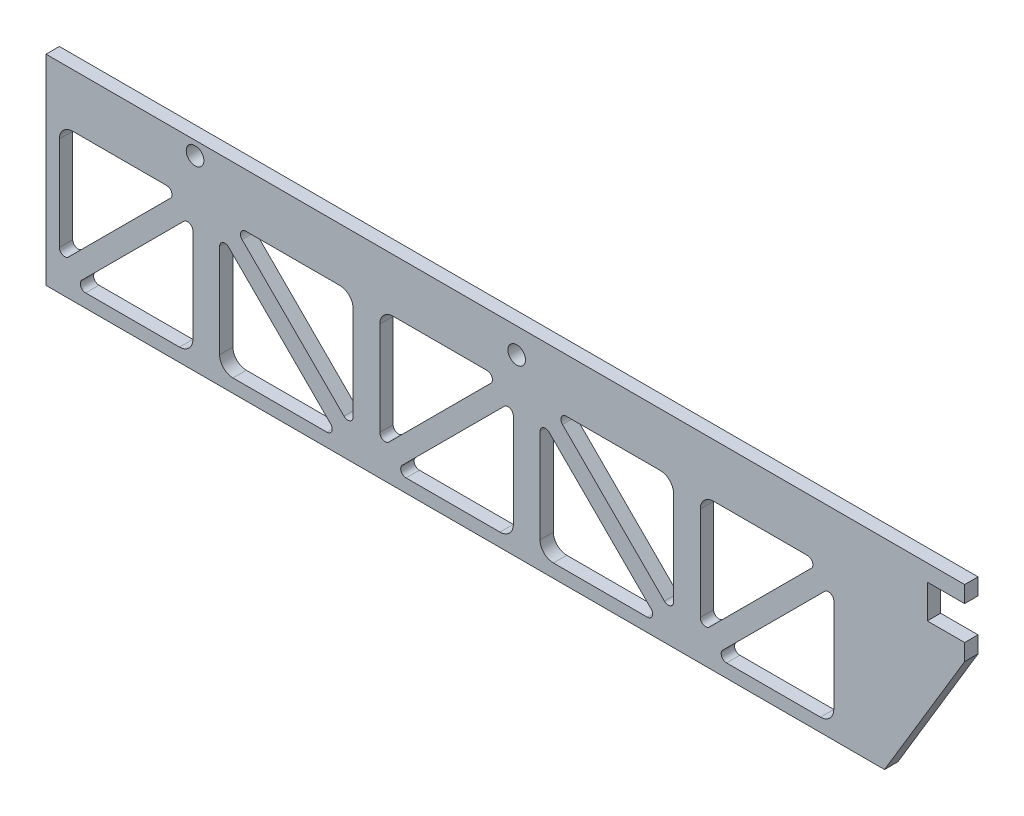
SolidWorks part; units mm, degrees
material "Balsa"
ref_plane "Front Plane" through (0, 0, 0) normal (0, 0, 1) x (1, 0, 0)
ref_plane "Top Plane" through (0, 0, 0) normal (0, 1, 0) x (1, 0, 0)
ref_plane "Right Plane" through (0, 0, 0) normal (1, 0, 0) x (0, 0, -1)
sketch "Model" plane through (0, 0, 0) normal (0, 0, 1) x (1, 0, 0)
  line L0 (74.8917, 92.9005) -> (74.8917, 84.8995)
  line L1 (74.8917, 84.8995) -> (66.8907, 84.8995)
  line L2 (66.8907, 84.8995) -> (66.8907, 92.9005)
  line L3 (66.8907, 92.9005) -> (74.8917, 92.9005)
  line L4 (227.7984, 87.3756) -> (227.7984, 79.375)
  line L5 (227.7984, 79.375) -> (219.7978, 79.375)
  line L6 (219.7978, 79.375) -> (219.7978, 87.3756)
  line L7 (219.7978, 87.3756) -> (227.7984, 87.3756)
  line L8 (171.2321, 6.35) -> (215.9, 6.35)
  line L9 (217.9139, 59.1639) -> (169.4361, 10.6861)
  line L10 (222.25, 57.3679) -> (222.25, 12.7)
  line L11 (234.95, 57.3679) -> (234.95, 12.7)
  line L12 (239.2861, 59.1639) -> (287.7639, 10.6861)
  line L13 (241.3, 6.35) -> (285.9679, 6.35)
  line L14 (294.1139, 17.0361) -> (245.6361, 65.5139)
  line L15 (247.4321, 69.85) -> (292.1, 69.85)
  line L16 (298.45, 63.5) -> (298.45, 18.8321)
  line L17 (323.6321, 6.35) -> (368.3, 6.35)
  line L18 (370.3139, 59.1639) -> (321.8361, 10.6861)
  line L19 (374.65, 57.3679) -> (374.65, 12.7)
  line L20 (18.8321, 6.35) -> (63.5, 6.35)
  line L21 (17.0361, 10.6861) -> (65.5139, 59.1639)
  line L22 (69.85, 57.3679) -> (69.85, 12.7)
  line L23 (82.55, 57.3679) -> (82.55, 12.7)
  line L24 (86.8861, 59.1639) -> (135.3639, 10.6861)
  line L25 (88.9, 6.35) -> (133.5679, 6.35)
  line L26 (93.2361, 65.5139) -> (141.7139, 17.0361)
  line L27 (95.0321, 69.85) -> (139.7, 69.85)
  line L28 (146.05, 63.5) -> (146.05, 18.8321)
  line L29 (163.0861, 17.0361) -> (211.5639, 65.5139)
  line L30 (158.75, 63.5) -> (158.75, 18.8321)
  line L31 (165.1, 69.85) -> (209.7679, 69.85)
  line L32 (315.4861, 17.0361) -> (363.9639, 65.5139)
  line L33 (311.15, 63.5) -> (311.15, 18.8321)
  line L34 (317.5, 69.85) -> (362.1679, 69.85)
  line L35 (419.1, 87.376) -> (419.1, 71.374)
  line L36 (436.88, 87.376) -> (419.1, 87.376)
  line L37 (436.88, 87.376) -> (436.88, 95.25)
  line L38 (0, 95.25) -> (436.88, 95.25)
  line L39 (0, 0) -> (0, 95.25)
  line L40 (0, 0) -> (398.78, 0)
  line L41 (436.88, 63.5) -> (398.78, 0)
  line L42 (436.88, 63.5) -> (436.88, 71.374)
  line L43 (419.1, 71.374) -> (436.88, 71.374)
  line L44 (6.35, 63.5) -> (6.35, 18.8321)
  line L45 (12.7, 69.85) -> (57.3679, 69.85)
  line L46 (59.1639, 65.5139) -> (10.6861, 17.0361)
  line L48 (168.656, 76.2) -> (321.056, 76.2) construction
  arc A0 (215.9, 6.35) -> (222.25, 12.7) centre (215.9, 12.7) ccw
  arc A1 (169.4361, 10.6861) -> (171.2321, 6.35) centre (171.2321, 8.89) ccw
  arc A2 (222.25, 57.3679) -> (217.9139, 59.1639) centre (219.71, 57.3679) ccw
  arc A3 (239.2861, 59.1639) -> (234.95, 57.3679) centre (237.49, 57.3679) ccw
  arc A4 (285.9679, 6.35) -> (287.7639, 10.6861) centre (285.9679, 8.89) ccw
  arc A5 (234.95, 12.7) -> (241.3, 6.35) centre (241.3, 12.7) ccw
  arc A6 (247.4321, 69.85) -> (245.6361, 65.5139) centre (247.4321, 67.31) ccw
  arc A7 (298.45, 63.5) -> (292.1, 69.85) centre (292.1, 63.5) ccw
  arc A8 (294.1139, 17.0361) -> (298.45, 18.8321) centre (295.91, 18.8321) ccw
  arc A9 (321.8361, 10.6861) -> (323.6321, 6.35) centre (323.6321, 8.89) ccw
  arc A10 (374.65, 57.3679) -> (370.3139, 59.1639) centre (372.11, 57.3679) ccw
  arc A11 (368.3, 6.35) -> (374.65, 12.7) centre (368.3, 12.7) ccw
  arc A12 (63.5, 6.35) -> (69.85, 12.7) centre (63.5, 12.7) ccw
  arc A13 (17.0361, 10.6861) -> (18.8321, 6.35) centre (18.8321, 8.89) ccw
  arc A14 (69.85, 57.3679) -> (65.5139, 59.1639) centre (67.31, 57.3679) ccw
  arc A15 (86.8861, 59.1639) -> (82.55, 57.3679) centre (85.09, 57.3679) ccw
  arc A16 (133.5679, 6.35) -> (135.3639, 10.6861) centre (133.5679, 8.89) ccw
  arc A17 (82.55, 12.7) -> (88.9, 6.35) centre (88.9, 12.7) ccw
  arc A18 (95.0321, 69.85) -> (93.2361, 65.5139) centre (95.0321, 67.31) ccw
  arc A19 (146.05, 63.5) -> (139.7, 69.85) centre (139.7, 63.5) ccw
  arc A20 (141.7139, 17.0361) -> (146.05, 18.8321) centre (143.51, 18.8321) ccw
  arc A21 (158.75, 18.8321) -> (163.0861, 17.0361) centre (161.29, 18.8321) ccw
  arc A22 (165.1, 69.85) -> (158.75, 63.5) centre (165.1, 63.5) ccw
  arc A23 (211.5639, 65.5139) -> (209.7679, 69.85) centre (209.7679, 67.31) ccw
  arc A24 (363.9639, 65.5139) -> (362.1679, 69.85) centre (362.1679, 67.31) ccw
  arc A25 (311.15, 18.8321) -> (315.4861, 17.0361) centre (313.69, 18.8321) ccw
  arc A26 (317.5, 69.85) -> (311.15, 63.5) centre (317.5, 63.5) ccw
  arc A27 (6.35, 18.8321) -> (10.6861, 17.0361) centre (8.89, 18.8321) ccw
  arc A28 (12.7, 69.85) -> (6.35, 63.5) centre (12.7, 63.5) ccw
  arc A29 (59.1639, 65.5139) -> (57.3679, 69.85) centre (57.3679, 67.31) ccw
  point P107 (223.7981, 83.3753)
  point P108 (219.7978, 83.3753)
  point P109 (223.7981, 79.375)
  point P110 (70.8912, 84.8995)
  point P111 (70.8912, 88.9)
  point P112 (74.8917, 88.9)
  dimension "D1" = 95.25
  dimension "D2" = 8.0006
  dimension "D3" = 153.0067
  dimension "D4" = 3.175
extrude "Boss-Extrude2" add sketch "Model" along normal blind 6.35
sketch "Sketch1" plane through (0, 0, 6.35) normal (0, 0, 1) x (1, 0, 0)
  line L0 (66.8907, 92.9005) -> (66.8907, 84.8995) construction
  line L1 (74.8917, 92.9005) -> (66.8907, 92.9005) construction
  line L2 (74.8917, 92.9005) -> (66.8907, 92.9005)
  line L3 (219.7978, 87.3756) -> (219.7978, 79.375) construction
  line L4 (66.6875, 93.1037) -> (75.0949, 93.1037)
  line L5 (66.6875, 93.1037) -> (66.6875, 84.6963)
  line L6 (66.6875, 84.6963) -> (75.0949, 84.6963)
  line L7 (75.0949, 93.1037) -> (75.0949, 84.6963)
  line L8 (219.6708, 87.5026) -> (228.0528, 87.5026)
  line L9 (219.6708, 87.5026) -> (219.6708, 79.1206)
  line L10 (219.6708, 79.1206) -> (228.0528, 79.1206)
  line L11 (228.0528, 87.5026) -> (228.0528, 79.1206)
  line L13 (227.7984, 87.3756) -> (219.7978, 87.3756) construction
  circle A0 centre (70.8912, 88.9) radius 4.2037
  circle A1 centre (223.8618, 83.3116) radius 4.191
  dimension "D1" = 8.4074
  dimension "D5" = 8.382
  dimension "D2" = 4.0005
  dimension "D3" = 8.001
  dimension "D4" = 4.0005
  dimension "D6" = 4.064
  dimension "D7" = 4.064
extrude "Boss-Extrude3" add sketch "Sketch1" against normal up to surface (6.35 mm away) contours A0 L4 L5 | A0 L7 L4 | A0 L6 L7 | A0 L5 L6 | A1 L9 L10 | A1 L8 L9 | A1 L11 L8 | A1 L10 L11 region at (74.1559, 92.1647, 6.35) region at (67.6265, 92.1647, 6.35) region at (74.1559, 85.6353, 6.35) region at (67.6265, 85.6353, 6.35) region at (220.607, 86.5664, 6.35) region at (227.1167, 86.5664, 6.35) region at (220.607, 80.0567, 6.35) region at (227.1167, 80.0567, 6.35) up to face at (70.8912, 88.9, 0)
extrude "Cut-Extrude1" cut sketch "Sketch1<3>" against normal up to surface (6.35 mm away) contours A0 L2 | A1 region at (70.8912, 88.874, 6.35) region at (223.8618, 83.3116, 6.35) up to face at (223.8076, 83.3658, 0)
sketch "Sketch1<3>" plane through (0, 0, 6.35) normal (0, 0, 1) x (1, 0, 0) same geometry as "Sketch1"
equation "\"D4@Sketch1\"=\"D3@Sketch1\"/2"
equation "\"D6@Sketch1\"=.16"
